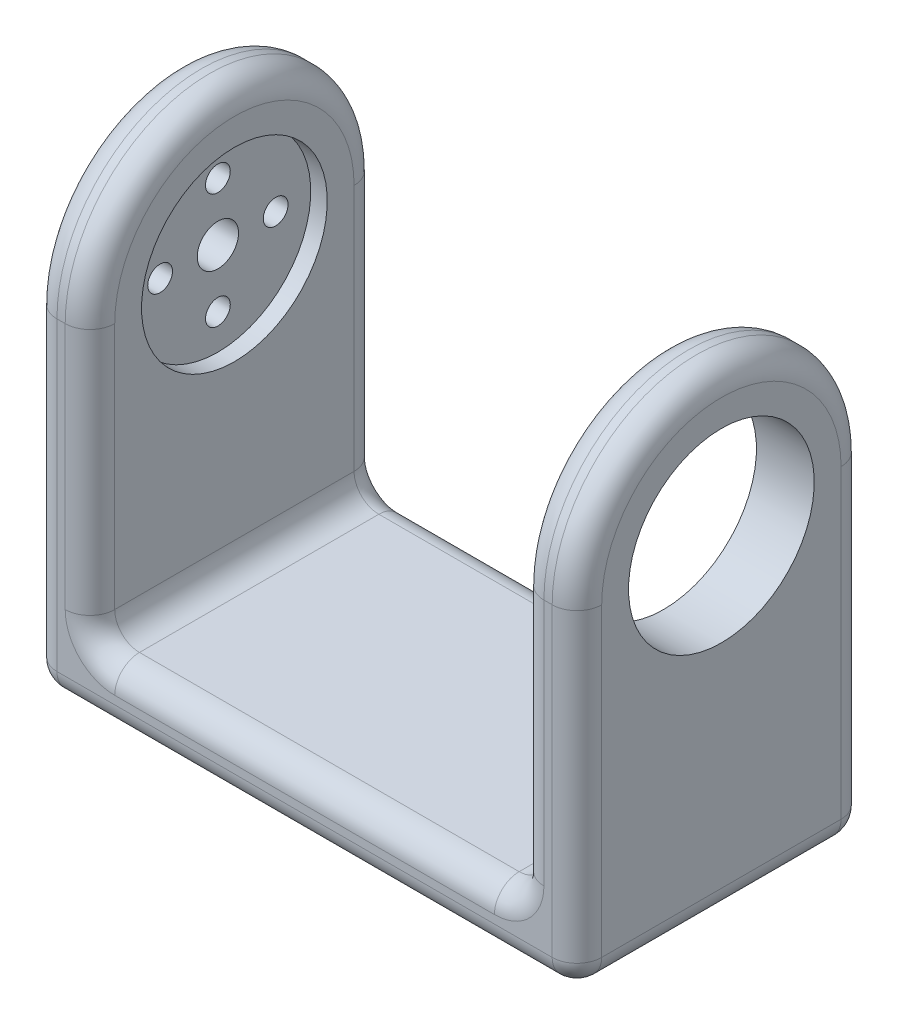
SolidWorks part; units mm, degrees
note: The reader was unsure of these and kept them because the rebuilt part matched: shared geometry of "Sketch3<3>", "Sketch3<4>", "Sketch3<5>", "Sketch4<3>".
material "Custom Plastic"
ref_plane "Front Plane" through (0, 0, 0) normal (0, 0, 1) x (1, 0, 0)
ref_plane "Top Plane" through (0, 0, 0) normal (0, 1, 0) x (1, 0, 0)
ref_plane "Right Plane" through (0, 0, 0) normal (1, 0, 0) x (0, 0, -1)
sketch "Sketch2" plane through (0, 0, 0) normal (0, 0, 1) x (1, 0, 0)
  line L2 (-33, 40) -> (-33, 0)
  line L3 (-33, 0) -> (33, 0)
  line L4 (33, 40) -> (33, 0)
  dimension "D1" = 40
  dimension "D2" = 66
extrude "Extrude-Thin1" add sketch "Sketch2" along normal mid plane 35 thin thin type one direction wall 7
sketch "Sketch3" plane through (-33, 0, 0) normal (-1, 0, 0) x (0, 0, 1)
  line L0 (17.5, 40) -> (-17.5, 40) construction
  line L1 (17.5, 0) -> (17.5, 40) construction
  circle A0 centre (0, 40) radius 17.5
  circle A1 centre (0, 40) radius 11.25
  line M6 (17.5, 40) -> (-17.5, 40)
  dimension "D1" = 22.5
extrude "Boss-Extrude2" add sketch "Sketch3" against normal up to surface (7 mm away) from surface at 0 contours A1 A0 M6 | A1 M6 up to face at (-26, 23.5, 0) starting at face at (-33, 20, 0)
extrude "Boss-Extrude3" add sketch "Sketch3<3>" against normal up to surface (7 mm away) from surface at -59 contours A1 M6 | A1 A0 M6 up to face at (33, 20, 0) starting at face at (26, 23.5, 0)
sketch "Sketch3<3>" plane through (-33, 0, 0) normal (-1, 0, 0) x (0, 0, 1) same geometry as "Sketch3"
fillet "Fillet1" radius 3 20 edges at (0, 7, 17.5) (0, 7, -17.5) (33, 20, 17.5) (33, 57.5, 0) (26, 57.5, 0) (33, 20, -17.5) (-33, 57.5, 0) (-33, 20, 17.5) (-33, 20, -17.5) (33, 0, 0) (-33, 0, 0) (0, 0, 17.5) (0, 0, -17.5) (26, 23.5, 17.5) (26, 7, 0) (26, 23.5, -17.5) (-26, 7, 0) (-26, 23.5, 17.5) (-26, 57.5, 0) (-26, 23.5, -17.5)
extrude "Cut-Extrude1" cut sketch "Sketch3<4>" along normal blind 2 from surface contours A1 M6 | A1 M6
sketch "Sketch3<4>" plane through (-33, 0, 0) normal (-1, 0, 0) x (0, 0, 1) same geometry as "Sketch3"
extrude "Cut-Extrude2" cut sketch "Sketch3<5>" against normal up to next from surface contours A1 M6 | A1 M6
sketch "Sketch3<5>" plane through (-33, 0, 0) normal (-1, 0, 0) x (0, 0, 1) same geometry as "Sketch3"
sketch "Sketch4" plane through (-28, 0, 0) normal (1, 0, 0) x (0, 0, -1)
  line L0 (0, 40) -> (7, 40) construction
  circle A0 centre (0, 40) radius 2.5
  circle A1 centre (0, 40) radius 11.25 construction
  circle A2 centre (7, 40) radius 1.5
  dimension "D1" = 5
  dimension "D3" = 3
  dimension "D2" = 7
extrude "Cut-Extrude3" cut sketch "Sketch4" against normal up to next contours A0
extrude "Cut-Extrude4" cut sketch "Sketch4<3>" against normal up to next contours A2
sketch "Sketch4<3>" plane through (-28, 0, 0) normal (1, 0, 0) x (0, 0, -1) same geometry as "Sketch4"
pattern_circular "CirPattern1" count 4 over 360 about axis through (0, 40, 0) along (1, 0, 0) of "Cut-Extrude4"
